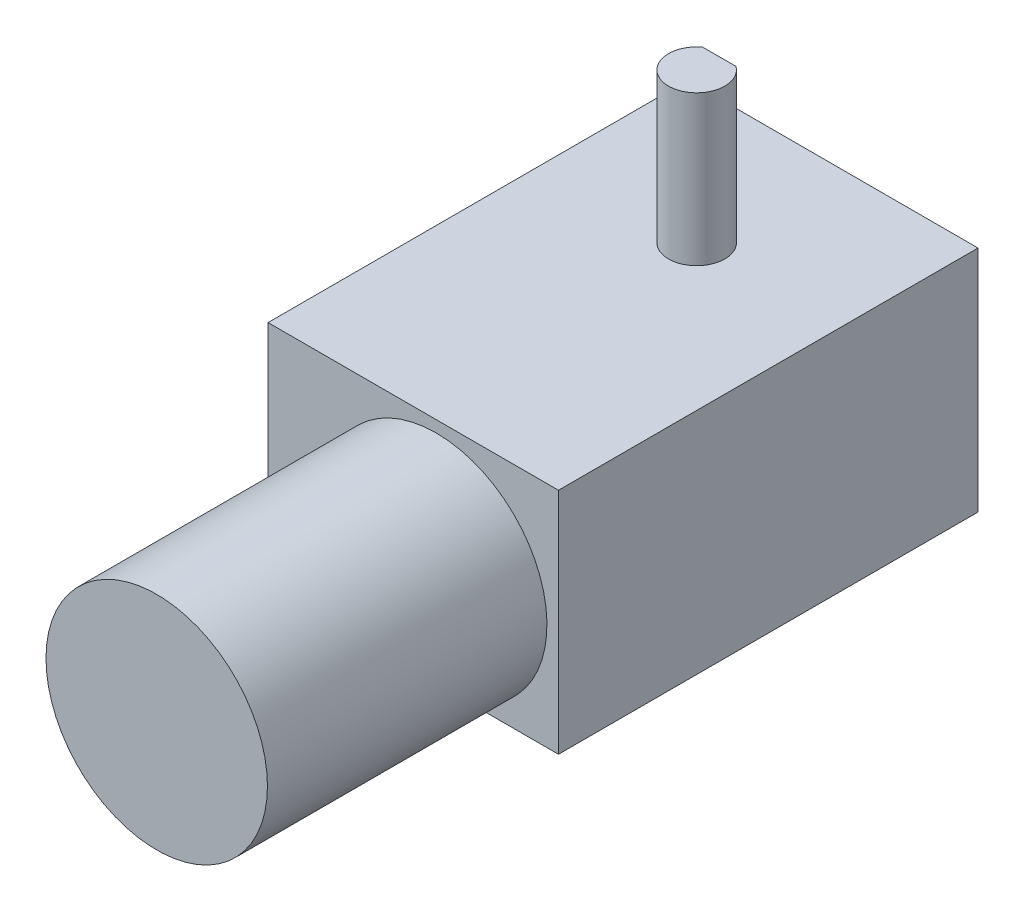
SolidWorks part; units mm, degrees
ref_plane "Front Plane" through (0, 0, 0) normal (0, 0, 1) x (1, 0, 0)
ref_plane "Top Plane" through (0, 0, 0) normal (0, 1, 0) x (1, 0, 0)
ref_plane "Right Plane" through (0, 0, 0) normal (1, 0, 0) x (0, 0, -1)
sketch "Sketch1" plane through (0, 0, 0) normal (0, 1, 0) x (1, 0, 0)
  line L0 (-1.833, 2.5) -> (1.833, 2.5)
  line L1 (-16, -31.228) -> (16, -31.228)
  line L2 (-16, -31.228) -> (-16, 15)
  line L3 (-16, 15) -> (16, 15)
  line L4 (16, -31.228) -> (16, 15)
  arc A0 (-1.833, 2.5) -> (1.833, 2.5) centre (0, 0) ccw
  point P5 (0, -31.228)
  dimension "D2" = 6.2
  dimension "D5" = 15
  dimension "D1" = 2.5
  dimension "D3" = 32
  dimension "D4" = 46.228
extrude "Boss-Extrude1" add sketch "Sketch1" along normal blind 25.2 contours L1 L4 L3 L2 A0 L0 | L0 A0 region at (0, 0, 0.1431) region at (0, 0, 8.2717)
extrude "Boss-Extrude2" add sketch "Sketch1<3>" along normal blind 16.5 from surface contours A0 L0 starting at face at (0, 25.2, 8.114)
sketch "Sketch1<3>" plane through (0, 0, 0) normal (0, 1, 0) x (1, 0, 0) same geometry as "Sketch1"
sketch "Sketch2" plane through (0, 0, 31.228) normal (0, 0, 1) x (1, 0, 0)
  line L2 (-4.9249, 23.93) -> (9.2293, 23.93) construction
  line L3 (9.2293, 23.93) -> (14.73, 18.245) construction
  line L4 (14.73, 18.245) -> (14.73, 6.3178) construction
  line L5 (-16, 25.2) -> (16, 25.2) construction
  line L6 (16, 25.2) -> (16, 0) construction
  circle A0 centre (2.53, 11.73) radius 12.2
  dimension "D1" = 24.4
  dimension "D2" = 1.27
  dimension "D3" = 1.27
extrude "Boss-Extrude3" add sketch "Sketch2" along normal blind 30.8
